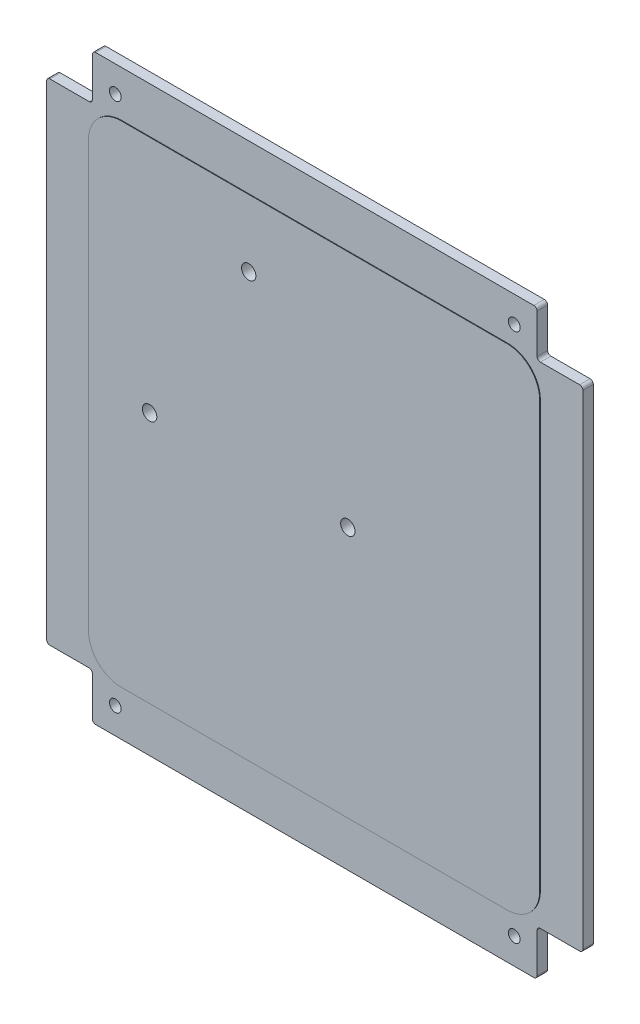
SolidWorks part; units mm, degrees
material "PET"
ref_plane "Front Plane" through (0, 0, 0) normal (0, 0, 1) x (1, 0, 0)
ref_plane "Top Plane" through (0, 0, 0) normal (0, 1, 0) x (1, 0, 0)
ref_plane "Right Plane" through (0, 0, 0) normal (1, 0, 0) x (0, 0, -1)
sketch "Sketch1" plane through (0, 0, 0) normal (0, 0, 1) x (1, 0, 0)
  line L0 (-34, 44) -> (-34, 38)
  line L1 (-33.5, -44.5) -> (33.5, -44.5)
  line L2 (-41, 37) -> (-41, -37)
  line L3 (-33.5, 44.5) -> (33.5, 44.5)
  line L4 (41, -37) -> (41, 37)
  line L5 (34, -44) -> (34, -38)
  line L6 (34.5, -37.5) -> (40.5, -37.5)
  line L7 (-34.5, 37.5) -> (-40.5, 37.5)
  line L8 (34, 44) -> (34, 38)
  line L9 (34.5, 37.5) -> (40.5, 37.5)
  line L10 (-40.5, -37.5) -> (-34.5, -37.5)
  line L11 (-34, -38) -> (-34, -44)
  line L12 (-34.5, -38) -> (34.5, 38) construction
  line L13 (34.5, -38) -> (-34.5, 38) construction
  arc A0 (-33.5, 44.5) -> (-34, 44) centre (-33.5, 44) ccw
  arc A1 (33.5, 44.5) -> (34, 44) centre (33.5, 44) cw
  arc A2 (34, 38) -> (34.5, 37.5) centre (34.5, 38) ccw
  arc A3 (40.5, 37.5) -> (41, 37) centre (40.5, 37) cw
  arc A4 (33.5, -44.5) -> (34, -44) centre (33.5, -44) ccw
  arc A5 (34.5, -37.5) -> (34, -38) centre (34.5, -38) ccw
  arc A6 (40.5, -37.5) -> (41, -37) centre (40.5, -37) ccw
  arc A7 (-34, -44) -> (-33.5, -44.5) centre (-33.5, -44) ccw
  arc A8 (-34, -38) -> (-34.5, -37.5) centre (-34.5, -38) ccw
  arc A9 (-41, -37) -> (-40.5, -37.5) centre (-40.5, -37) ccw
  arc A10 (-40.5, 37.5) -> (-41, 37) centre (-40.5, 37) ccw
  arc A11 (-34.5, 37.5) -> (-34, 38) centre (-34.5, 38) ccw
  point P0 (0, 0)
  dimension "D4" = 0.5
  dimension "D1" = 7
  dimension "D2" = 7
  dimension "D3" = 7
  dimension "D5" = 7
  dimension "D6" = 7
  dimension "D7" = 7
  dimension "D8" = 7
  dimension "D9" = 7
  dimension "D10" = 89
  dimension "D11" = 82
extrude "Boss-Extrude1" add sketch "Sketch1" along normal blind 1.6
sketch "Esboço1" plane through (0, 0, 1.6) normal (0, 0, 1) x (1, 0, 0)
  line L1 (-29.5, -37.5) -> (29.5, -37.5)
  line L2 (-34.5, -32.5) -> (-34.5, 32.5)
  line L3 (-29.5, 37.5) -> (29.5, 37.5)
  line L4 (34.5, -32.5) -> (34.5, 32.5)
  line L5 (-29.5, -32.5) -> (29.5, 32.5) construction
  line L6 (-29.5, 32.5) -> (29.5, -32.5) construction
  arc A0 (-34.5, 32.5) -> (-29.5, 37.5) centre (-29.5, 32.5) cw
  arc A1 (29.5, 37.5) -> (34.5, 32.5) centre (29.5, 32.5) cw
  arc A2 (34.5, -32.5) -> (29.5, -37.5) centre (29.5, -32.5) cw
  arc A3 (-29.5, -37.5) -> (-34.5, -32.5) centre (-29.5, -32.5) cw
  point P0 (0, 0)
  dimension "D1" = 5
  dimension "D2" = 69
  dimension "D3" = 75
extrude "Boss-Extrude2" add sketch "Esboço1" along normal blind 0.1
hole_wizard "M1.6 Hole1-FixingStructure" positions "Sketch3" profile "Sketch2" hole size "M1.6" standard "DIN"
sketch "Sketch3" plane through (0, 0, 0) normal (0, 0, -1) x (-1, 0, 0)
  line L0 (-33.5, 44.5) -> (33.5, 44.5) construction
  line L1 (33.5, -44.5) -> (-33.5, -44.5) construction
  line L2 (-41, -37) -> (-41, 37) construction
  line L3 (41, 37) -> (41, -37) construction
  point P0 (-30.5, 40.5)
  point P2 (30.5, 40.5)
  point P4 (-30.5, -40.5)
  point P6 (30.5, -40.5)
  dimension "D1" = 4
  dimension "D2" = 4
  dimension "D3" = 10.5
  dimension "D4" = 10.5
sketch "Sketch2" plane through (30.5, 40.5, 0) normal (1, 0, 0) x (0, 1, 0)
  line L0 (0, 0) -> (0, 200.5408)
  line L1 (0, 200.5408) -> (0.9, 200)
  line L2 (0.9, 200) -> (0.9, 0)
  line L5 (0.9, 0) -> (0, 0)
  line L10 (0, 200.5408) -> (-0.9, 200) construction
  line L11 (0, -6.35) -> (0, 107.95) construction
  dimension "Hole Dia." = 1.8
  dimension "Hole Depth" = 200
  dimension "Drill Angle" = 118
sketch "Sketch4" plane through (0, 0, 1.7) normal (0, 0, 1) x (1, 0, 0)
  circle A0 centre (-25.1554, 1) radius 1.1 construction
  circle A1 centre (-10, 27.25) radius 1.1 construction
  circle A2 centre (5.1554, 1) radius 1.1 construction
  circle A3 centre (-25.1554, 1) radius 1.1
  circle A4 centre (-10, 27.25) radius 1.1
  circle A5 centre (5.1554, 1) radius 1.1
extrude "Cut-Extrude1" cut sketch "Sketch4" against normal up to surface (1.7 mm away) up to face at (29.6, 40.5, 0)
